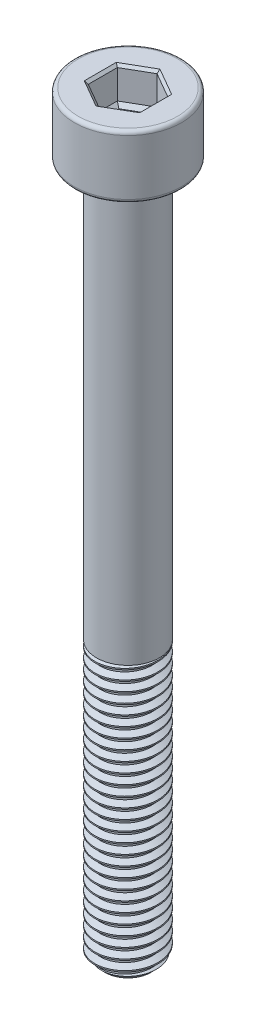
SolidWorks part; units mm, degrees
material "AISI Type A2 Tool Steel"
ref_plane "Front Plane" through (0, 0, 0) normal (0, 0, 1) x (1, 0, 0)
ref_plane "Top Plane" through (0, 0, 0) normal (0, 1, 0) x (1, 0, 0)
ref_plane "Right Plane" through (0, 0, 0) normal (1, 0, 0) x (0, 0, -1)
sketch "Sketch1" plane through (0, 0, 0) normal (0, 1, 0) x (1, 0, 0)
  circle A0 centre (0, 0) radius 2.5
  dimension "D1" = 5
extrude "Boss-Extrude1" add sketch "Sketch1" along normal blind 22
thread "Thread1" pitch 0.8 method cut profile "Thread Profile1" start angle 0, offset 1, length 0, pitch 0.8, diameter 5
ref_plane "Plane1" through (-2.5, 23, 0) normal (0, 0, 1) x (-1, 0, 0)
sketch "Thread Profile1" plane through (-2.5, 23, 0) normal (0, 0, 1) x (-1, 0, 0)
  line L0 (0, 0) -> (0, 0.8) construction
  line L11 (0, 0) -> (0, 0.7)
  line L12 (0, 0.7) -> (-0.433, 0.45)
  line L13 (-0.433, 0.45) -> (-0.433, 0.25)
  line L15 (-0.433, 0.25) -> (0, 0)
  line L17 (-0.433, 0.35) -> (0, 0.35) construction
  point P2 (0, 0)
  dimension "Pitch" = 0.8
  dimension "Profile_Angle" = 60
  dimension "Profile_Land" = 0.2
  dimension "Profile_Height" = 0.433
sketch "Sketch2" plane through (0, 22, 0) normal (0, 1, 0) x (1, 0, 0)
  circle A0 centre (0, 0) radius 2.5
  dimension "D1" = 5
extrude "Boss-Extrude2" add sketch "Sketch2" along normal blind 33
sketch "Sketch3" plane through (0, 55, 0) normal (0, 1, 0) x (1, 0, 0)
  circle A0 centre (0, 0) radius 4.25
  dimension "D1" = 8.5
extrude "Boss-Extrude3" add sketch "Sketch3" along normal blind 5
fillet "Fillet1" radius 0.3 2 edges at (0, 55, 4.25) (0, 60, 4.25)
sketch "Sketch4" plane through (0, 0, 0) normal (0, 0, 1) x (1, 0, 0)
  line L0 (0, 0) -> (0, 0.4416) construction
  line L1 (0, 0) -> (2.51, 0) construction
  line L2 (2.51, 0) -> (2.51, 0.7)
  line L3 (2.51, 0.7) -> (1.81, 0)
  line L4 (1.81, 0) -> (2.51, 0)
  dimension "D1" = 0.7
  dimension "D2" = 45
  dimension "D3" = 2.51
revolve "Cut-Revolve1" cut sketch "Sketch4" angle 360 about L0
sketch "Sketch5" plane through (0, 60, 0) normal (0, 1, 0) x (1, 0, 0)
  line L1 (0, 2.3094) -> (-2, 1.1547)
  line L2 (-2, 1.1547) -> (-2, -1.1547)
  line L3 (-2, -1.1547) -> (0, -2.3094)
  line L4 (0, -2.3094) -> (2, -1.1547)
  line L5 (2, -1.1547) -> (2, 1.1547)
  line L6 (2, 1.1547) -> (0, 2.3094)
  circle A0 centre (0, 0) radius 2 construction
  dimension "D1" = 4
extrude "Cut-Extrude1" cut sketch "Sketch5" against normal blind 2.5
chamfer "Chamfer1" distance 0.2 angle 45 6 edges at (-1, 60, 1.7321) (1, 60, 1.7321) (2, 60, 0) (1, 60, -1.7321) (-1, 60, -1.7321) (-2, 60, 0)
sketch "Sketch6" plane through (0, 57.5, 0) normal (0, 1, 0) x (1, 0, 0)
  line L1 (0, 2.3094) -> (-2, 1.1547)
  line L2 (-2, 1.1547) -> (-2, -1.1547)
  line L3 (-2, -1.1547) -> (0, -2.3094)
  line L4 (0, -2.3094) -> (2, -1.1547)
  line L5 (2, -1.1547) -> (2, 1.1547)
  line L6 (2, 1.1547) -> (0, 2.3094)
  circle A0 centre (0, 0) radius 2 construction
extrude "Cut-Extrude2" cut sketch "Sketch6" against normal blind 0.3 draft 45
